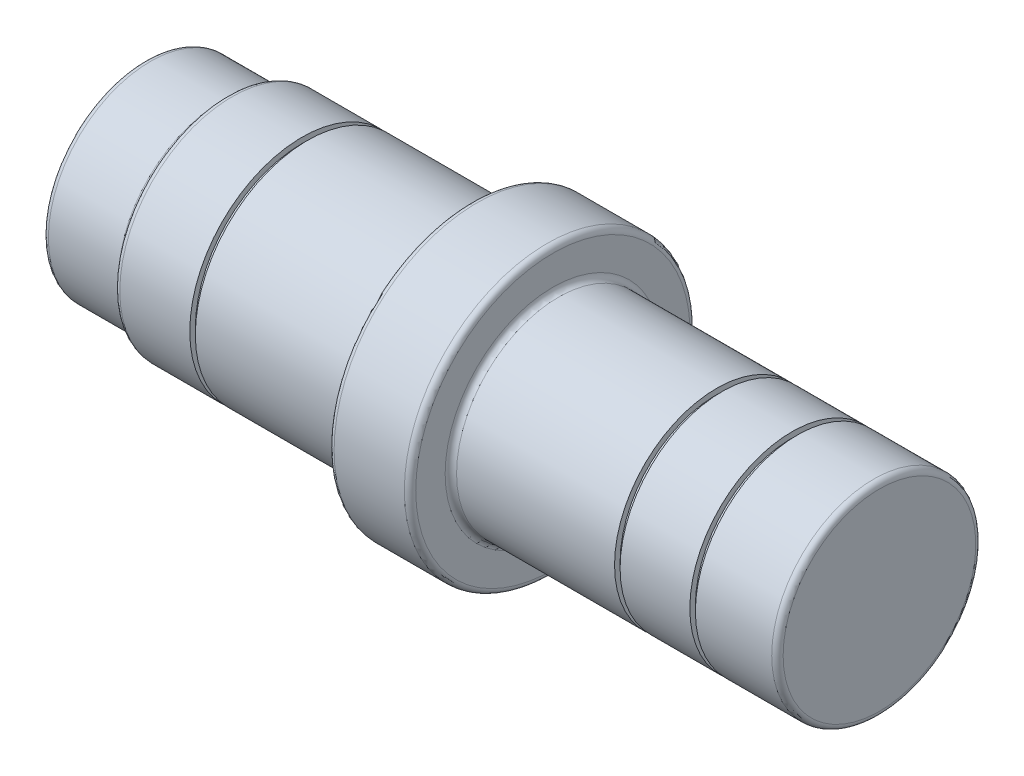
SolidWorks part; units mm, degrees
ref_plane "Front Plane" through (0, 0, 0) normal (0, 0, 1) x (1, 0, 0)
ref_plane "Top Plane" through (0, 0, 0) normal (0, 1, 0) x (1, 0, 0)
ref_plane "Right Plane" through (0, 0, 0) normal (1, 0, 0) x (0, 0, -1)
sketch "Sketch1" plane through (0, 0, 0) normal (0, 1, 0) x (1, 0, 0)
  line L0 (0, 0) -> (0, 29.972)
  line L5 (1.778, 31.75) -> (23.622, 31.75)
  line L6 (0, 0) -> (228.6, 0)
  line L7 (25.4, 33.528) -> (25.4, 33.147)
  line L8 (27.178, 34.925) -> (99.822, 34.925)
  line L9 (101.6, 36.703) -> (101.6, 42.672)
  line L10 (103.378, 44.45) -> (125.222, 44.45)
  line L11 (127, 42.672) -> (127, 33.528)
  line L12 (128.778, 31.75) -> (226.822, 31.75)
  line L13 (228.6, 29.972) -> (228.6, 0)
  line L14 (63.5, 0) -> (88.9, 0) construction
  line L15 (101.6, 34.925) -> (50.8, 34.925)
  line L16 (101.6, 34.925) -> (101.6, 0)
  line L17 (101.6, 0) -> (50.8, 0)
  line L18 (50.8, 34.925) -> (50.8, 0)
  line L19 (101.6, 34.925) -> (50.8, 0) construction
  line L20 (101.6, 0) -> (50.8, 34.925) construction
  line L21 (127, 31.75) -> (177.8, 31.75)
  line L22 (127, 31.75) -> (127, 0)
  line L23 (127, 0) -> (177.8, 0)
  line L24 (177.8, 31.75) -> (177.8, 0)
  line L25 (127, 31.75) -> (177.8, 0) construction
  line L26 (127, 0) -> (177.8, 31.75) construction
  line L27 (63.5, 6.35) -> (88.9, 6.35)
  line L28 (63.5, -6.35) -> (88.9, -6.35)
  line L29 (76.2, 0) -> (76.2, 17.4625) construction
  line L30 (139.7, 0) -> (165.1, 0) construction
  line L31 (139.7, 6.35) -> (165.1, 6.35)
  line L32 (139.7, -6.35) -> (165.1, -6.35)
  line L33 (152.4, 0) -> (152.4, 15.875) construction
  line L35 (50.673, 34.925) -> (48.9458, 34.925)
  line L36 (50.673, 34.925) -> (50.673, 33.1978)
  line L37 (50.673, 33.1978) -> (48.9458, 33.1978)
  line L38 (48.9458, 34.925) -> (48.9458, 33.1978)
  line L39 (50.673, 34.925) -> (48.9458, 33.1978) construction
  line L40 (50.673, 33.1978) -> (48.9458, 34.925) construction
  line L41 (177.927, 31.75) -> (179.6542, 31.75)
  line L42 (177.927, 31.75) -> (177.927, 30.0228)
  line L43 (177.927, 30.0228) -> (179.6542, 30.0228)
  line L44 (179.6542, 31.75) -> (179.6542, 30.0228)
  line L45 (177.927, 31.75) -> (179.6542, 30.0228) construction
  line L46 (177.927, 30.0228) -> (179.6542, 31.75) construction
  line L47 (203.073, 31.75) -> (201.3458, 31.75)
  line L48 (203.073, 31.75) -> (203.073, 30.0228)
  line L49 (203.073, 30.0228) -> (201.3458, 30.0228)
  line L50 (201.3458, 31.75) -> (201.3458, 30.0228)
  line L51 (203.073, 31.75) -> (201.3458, 30.0228) construction
  line L52 (203.073, 30.0228) -> (201.3458, 31.75) construction
  arc A0 (63.5, 6.35) -> (63.5, -6.35) centre (63.5, 0) ccw
  arc A1 (88.9, -6.35) -> (88.9, 6.35) centre (88.9, 0) ccw
  arc A2 (139.7, 6.35) -> (139.7, -6.35) centre (139.7, 0) ccw
  arc A3 (165.1, -6.35) -> (165.1, 6.35) centre (165.1, 0) ccw
  arc A4 (0, 29.972) -> (1.778, 31.75) centre (1.778, 29.972) cw
  arc A5 (228.6, 29.972) -> (226.822, 31.75) centre (226.822, 29.972) ccw
  arc A6 (127, 33.528) -> (128.778, 31.75) centre (128.778, 33.528) ccw
  arc A7 (125.222, 44.45) -> (127, 42.672) centre (125.222, 42.672) cw
  arc A8 (103.378, 44.45) -> (101.6, 42.672) centre (103.378, 42.672) ccw
  arc A9 (27.178, 34.925) -> (25.4, 33.147) centre (27.178, 33.147) ccw
  arc A10 (99.822, 34.925) -> (101.6, 36.703) centre (99.822, 36.703) ccw
  arc A11 (23.622, 31.75) -> (25.4, 33.528) centre (23.622, 33.528) ccw
  point P15 (76.2, 17.4625)
  point P19 (152.4, 15.875)
  point P22 (76.2, 0)
  point P31 (152.4, 0)
  point P40 (0, 31.75)
  point P43 (228.6, 31.75)
  point P49 (127, 44.45)
  point P52 (101.6, 44.45)
  point P55 (25.4, 34.925)
  point P61 (25.4, 31.75)
  point P66 (49.8094, 34.0614)
  point P71 (178.7906, 30.8864)
  point P75 (202.2094, 30.8864)
  dimension "D15" = 1.778
  dimension "D1" = 31.75
  dimension "D2" = 34.925
  dimension "D3" = 25.4
  dimension "D4" = 76.2
  dimension "D5" = 25.4
  dimension "D6" = 44.45
  dimension "D7" = 31.75
  dimension "D8" = 101.6
  dimension "D9" = 50.8
  dimension "D10" = 50.8
  dimension "D11" = 25.4
  dimension "D12" = 12.7
  dimension "D13" = 12.7
  dimension "D14" = 25.4
  dimension "D16" = 0.127
  dimension "D17" = 1.7272
  dimension "D18" = 0.127
  dimension "D19" = 25.527
revolve "Revolve1" add sketch "Sketch1" angle 360 about L6 region at (25.9727, 0, -16.6691) region at (76.2, 0, -19.5533) region at (76.2, 0, -3.0397) region at (114.3, 0, -22.2126) region at (152.4, 0, -17.9518) region at (203.2366, 0, -15.8127)
extrude "Cut-Extrude1" cut sketch "Sketch1<7>" against normal through all from offset 28.575 contours L28 A1 L17 A0 | L27 A1 L28 A0 region at (76.2, 0, 3.0397) offset against normal yes
sketch "Sketch1<7>" plane through (0, 0, 0) normal (0, 1, 0) x (1, 0, 0) same geometry as "Sketch1"
extrude "Cut-Extrude2" cut sketch "Sketch1<10>" against normal up to next from offset 25.4 contours L32 A3 L31 A2 offset against normal yes
sketch "Sketch1<10>" plane through (0, 0, 0) normal (0, 1, 0) x (1, 0, 0) same geometry as "Sketch1"
